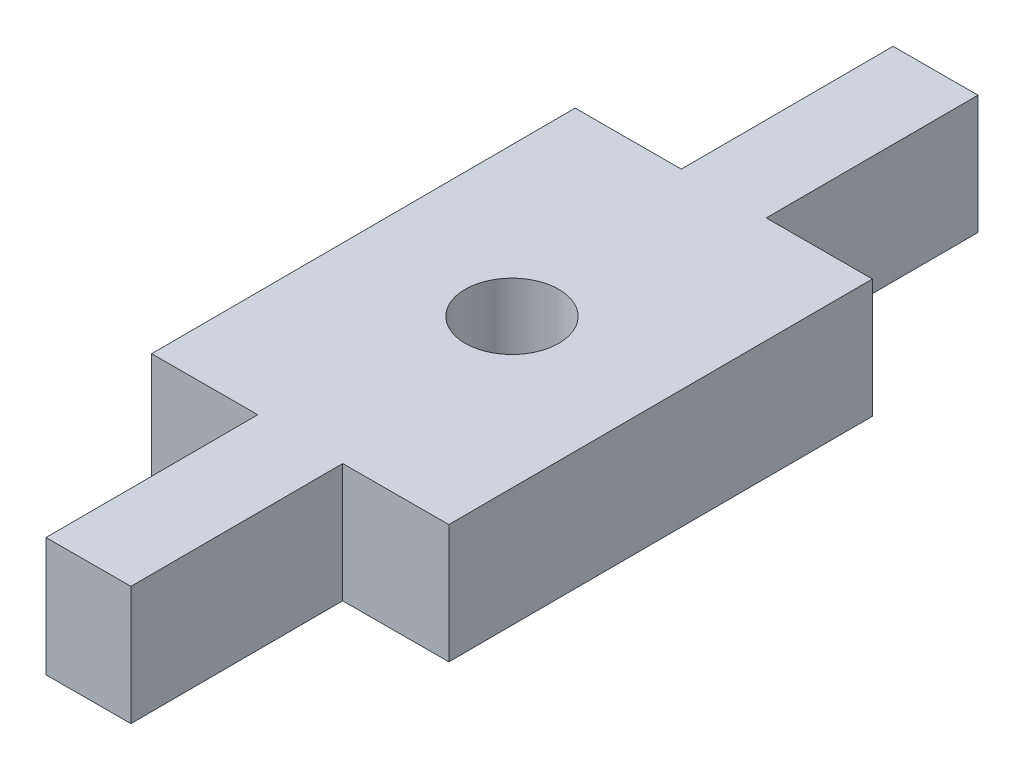
SolidWorks part; units mm, degrees
material "Acrylic (Medium-high impact)"
ref_plane "Front Plane" through (0, 0, 0) normal (0, 0, 1) x (1, 0, 0)
ref_plane "Top Plane" through (0, 0, 0) normal (0, 1, 0) x (1, 0, 0)
ref_plane "Right Plane" through (0, 0, 0) normal (1, 0, 0) x (0, 0, -1)
sketch "Sketch1" plane through (0, 0, 0) normal (0, 1, 0) x (1, 0, 0)
  line L0 (-1.118, -5.6688) -> (-1.1057, -11.3351)
  line L1 (-1.1057, -11.3351) -> (1.1567, -11.3301)
  line L2 (1.1567, -11.3301) -> (1.1444, -5.6639)
  line L3 (1.1444, -5.6639) -> (3.9726, -5.6577)
  line L4 (3.9726, -5.6577) -> (3.9478, 5.6747)
  line L5 (3.9478, 5.6747) -> (1.1198, 5.6685)
  line L6 (1.1198, 5.6685) -> (1.1074, 11.3347)
  line L7 (1.1074, 11.3347) -> (-1.1548, 11.3298)
  line L8 (-1.1548, 11.3298) -> (-1.1425, 5.6636)
  line L9 (-1.1425, 5.6636) -> (-3.9708, 5.6574)
  line L10 (-3.9708, 5.6574) -> (-3.9461, -5.675)
  line L11 (-3.9461, -5.675) -> (-1.118, -5.6688)
  line L12 (-0.8851, 0.8829) -> (0.8851, -0.8827) construction
  circle A0 centre (0, 0) radius 1.25
  dimension "D1" = 2.5
extrude "Boss-Extrude1" add sketch "Sketch1" along normal blind 3.175
